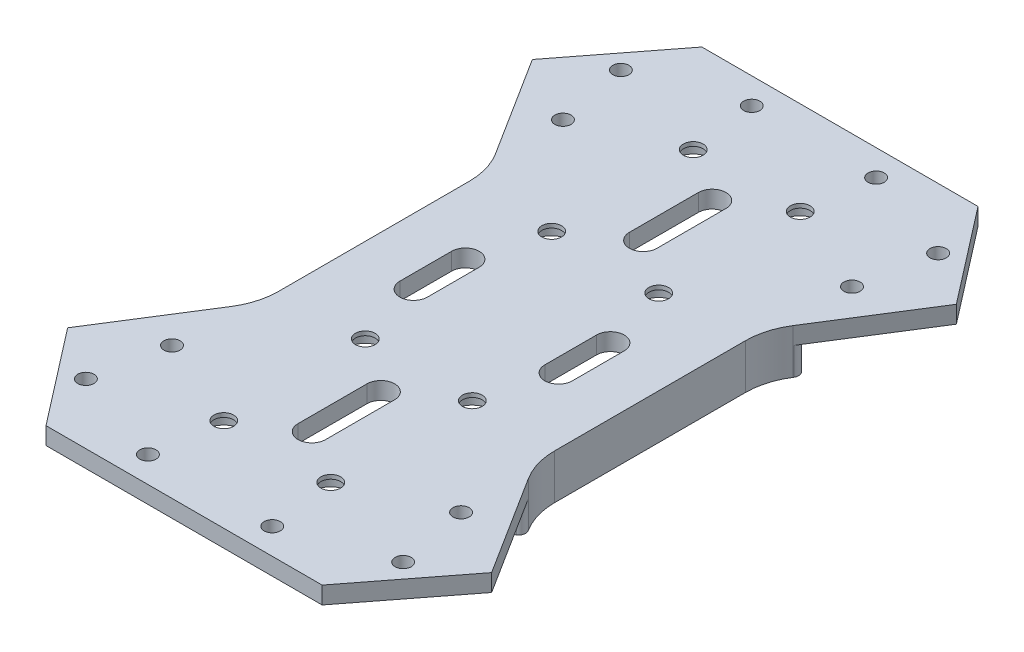
SolidWorks part; units mm, degrees
ref_plane "Plan de face" through (0, 0, 0) normal (0, 0, 1) x (1, 0, 0)
ref_plane "Plan de dessus" through (0, 0, 0) normal (0, 1, 0) x (1, 0, 0)
ref_plane "Plan de droite" through (0, 0, 0) normal (1, 0, 0) x (0, 0, -1)
sketch "Esquisse1" plane through (0, 0, 0) normal (0, 1, 0) x (1, 0, 0)
  line L0 (0, 95) -> (0, -95) construction
  line L1 (40, -95) -> (-40, -95)
  line L2 (-40, -95) -> (-61.4148, -67.316)
  line L3 (-61.4148, -67.316) -> (-40, -33.4103)
  line L4 (-40, -33.4103) -> (-40, 33.4103)
  line L5 (-40, 33.4103) -> (-61.4148, 67.316)
  line L6 (-61.4148, 67.316) -> (-40, 95)
  line L7 (-40, 95) -> (40, 95)
  line L8 (-40, -95) -> (-40, 95) construction
  line L9 (-90.2912, 0) -> (0, 0) construction
  line L10 (50.7074, 81.158) -> (185.1727, 185.1727) construction
  line L11 (-50.7074, 81.158) -> (-185.1727, 185.1727) construction
  line L12 (40, -95) -> (40, 95) construction
  line L13 (61.4148, 67.316) -> (40, 95)
  line L14 (40, 33.4103) -> (61.4148, 67.316)
  line L15 (40, -33.4103) -> (40, 33.4103)
  line L16 (61.4148, -67.316) -> (40, -33.4103)
  line L17 (40, -95) -> (61.4148, -67.316)
  line L18 (50.7074, -81.158) -> (185.1727, -185.1727) construction
  line L19 (-50.7074, -81.158) -> (-185.1727, -185.1727) construction
  line L20 (-185.1727, 185.1727) -> (185.1727, 185.1727) construction
  line L21 (-185.1727, 185.1727) -> (-185.1727, -185.1727) construction
  line L22 (-50.7074, 81.158) -> (-11.4576, 50.7965) construction
  circle A0 centre (18.0097, 87.4716) radius 2.35
  circle A1 centre (45.9616, 77.4869) radius 2.35
  circle A2 centre (41.8719, 56.6236) radius 2.35
  circle A3 centre (-41.8719, 56.6236) radius 2.35
  circle A4 centre (-45.9616, 77.4869) radius 2.35
  circle A5 centre (-18.0097, 87.4716) radius 2.35
  circle A6 centre (41.8719, -56.6236) radius 2.35
  circle A7 centre (45.9616, -77.4869) radius 2.35
  circle A8 centre (18.0097, -87.4716) radius 2.35
  circle A9 centre (-18.0097, -87.4716) radius 2.35
  circle A10 centre (-45.9616, -77.4869) radius 2.35
  circle A11 centre (-41.8719, -56.6236) radius 2.35
  dimension "D10" = 4.7
  dimension "D11" = 4.7
  dimension "D12" = 4.7
  dimension "D1" = 40
  dimension "D2" = 190
  dimension "D3" = 110
  dimension "D4" = 35
  dimension "D5" = 170
  dimension "D6" = 170
  dimension "D7" = 170
  dimension "D8" = 170
  dimension "D9" = 127.724
extrude "Boss.-Extru.1" add sketch "Esquisse1" along normal blind 5
sketch3d "Esquisse3D2" plane through (0, 0, 0) normal (0, 0, 1) x (1, 0, 0)
sketch "Esquisse2" plane through (0, 0, 0) normal (0, -1, 0) x (1, 0, 0)
  line L0 (0, -95) -> (0, 69.3313) construction
  line L1 (-36.2914, -47.5) -> (35.8719, -47.5) construction
  line L2 (40, -95) -> (-40, -95) construction
  line L3 (-47.7044, 0) -> (47.4513, 0) construction
  circle A0 centre (-15.5, -68) radius 5.5
  circle A1 centre (15.5, -68) radius 5.5
  circle A2 centre (15.5, -27) radius 5.5
  circle A3 centre (-15.5, -27) radius 5.5
  circle A4 centre (15.5, 68) radius 5.5
  circle A5 centre (-15.5, 68) radius 5.5
  circle A6 centre (15.5, 27) radius 5.5
  circle A7 centre (-15.5, 27) radius 5.5
  dimension "D1" = 11
  dimension "D2" = 15.5
  dimension "D3" = 20.5
extrude "Enlèv. mat.-Extru.1" cut sketch "Esquisse2" against normal blind 3.8
sketch "Esquisse3" plane through (0, 0, 0) normal (0, -1, 0) x (1, 0, 0)
  line L0 (-48.0842, 0) -> (48.5909, 0) construction
  circle A0 centre (-15.5, -27) radius 2.85
  circle A1 centre (15.5, -27) radius 2.85
  circle A2 centre (-15.5, -68) radius 2.85
  circle A3 centre (15.5, -68) radius 2.85
  circle A4 centre (15.5, 68) radius 2.85
  circle A5 centre (-15.5, 68) radius 2.85
  circle A6 centre (15.5, 27) radius 2.85
  circle A7 centre (-15.5, 27) radius 2.85
  dimension "D1" = 5.7
  dimension "D2" = 5.7
  dimension "D3" = 5.7
  dimension "D4" = 5.7
extrude "Enlèv. mat.-Extru.2" cut sketch "Esquisse3" against normal blind 5
sketch "Esquisse5" plane through (0, 0, 0) normal (0, -1, 0) x (1, 0, 0)
  line L0 (0, -105.2031) -> (0, 102.0565) construction
  line L1 (0, 58) -> (0, 38) construction
  line L2 (4, 58) -> (4, 38)
  line L3 (-4, 58) -> (-4, 38)
  line L4 (-46.5705, 0) -> (46.5705, 0) construction
  line L5 (-21, -7.5) -> (-21, 7.5) construction
  line L6 (-25, -7.5) -> (-25, 7.5)
  line L7 (-17, -7.5) -> (-17, 7.5)
  line L8 (21, -7.5) -> (21, 7.5) construction
  line L9 (25, -7.5) -> (25, 7.5)
  line L10 (17, -7.5) -> (17, 7.5)
  line L11 (-35.7675, 10) -> (32.6735, 10) construction
  line L15 (0, -58) -> (0, -38) construction
  line L16 (4, -58) -> (4, -38)
  line L17 (-4, -58) -> (-4, -38)
  arc A0 (4, 58) -> (-4, 58) centre (0, 58) ccw
  arc A1 (-4, 38) -> (4, 38) centre (0, 38) ccw
  arc A2 (-25, -7.5) -> (-17, -7.5) centre (-21, -7.5) ccw
  arc A3 (-17, 7.5) -> (-25, 7.5) centre (-21, 7.5) ccw
  arc A4 (25, -7.5) -> (17, -7.5) centre (21, -7.5) cw
  arc A5 (17, 7.5) -> (25, 7.5) centre (21, 7.5) cw
  arc A8 (4, -58) -> (-4, -58) centre (0, -58) cw
  arc A9 (-4, -38) -> (4, -38) centre (0, -38) cw
  point P5 (0, 48)
  point P15 (-21, 0)
  point P23 (21, 0)
  point P37 (0, -48)
  dimension "D1" = 8
  dimension "D2" = 20
  dimension "D3" = 48
  dimension "D6" = 8
  dimension "D8" = 10
  dimension "D4" = 21
  dimension "D5" = 15
extrude "Enlèv. mat.-Extru.3" cut sketch "Esquisse5" against normal blind 5
sketch "Esquisse6" plane through (0, 0, 0) normal (0, -1, 0) x (1, 0, 0)
  line L0 (40, -33.4103) -> (40, 33.4103)
  line L1 (40, 33.4103) -> (44.272, 40.1741)
  line L2 (44.272, 40.1741) -> (40.8901, 42.3102)
  line L3 (40.8901, 42.3102) -> (36, 34.5677)
  line L4 (36, 34.5677) -> (36, -34.5677)
  line L5 (40, -33.4103) -> (44.272, -40.1741)
  line L6 (44.272, -40.1741) -> (40.8901, -42.3102)
  line L7 (40.8901, -42.3102) -> (36, -34.5677)
  line L8 (40, 33.4103) -> (40, -33.4103) construction
  line L9 (61.4148, 67.316) -> (40, 33.4103) construction
  line L10 (40, -33.4103) -> (61.4148, -67.316) construction
  line L11 (0, -75.9337) -> (0, 75.2034) construction
  line L12 (-40.8901, -42.3102) -> (-36, -34.5677)
  line L13 (-44.272, -40.1741) -> (-40.8901, -42.3102)
  line L14 (-40, -33.4103) -> (-44.272, -40.1741)
  line L15 (-36, 34.5677) -> (-36, -34.5677)
  line L16 (-40.8901, 42.3102) -> (-36, 34.5677)
  line L17 (-44.272, 40.1741) -> (-40.8901, 42.3102)
  line L18 (-40, 33.4103) -> (-44.272, 40.1741)
  line L19 (-40, -33.4103) -> (-40, 33.4103)
  dimension "D1" = 4
  dimension "D2" = 4
  dimension "D3" = 4
  dimension "D4" = 8
  dimension "D5" = 8
extrude "Boss.-Extru.2" add sketch "Esquisse6" along normal blind 8
fillet "Congé2" radius 2 8 edges at (-40.8901, -4, 42.3102) (-44.272, -4, 40.1741) (-44.272, -4, -40.1741) (-40.8901, -4, -42.3102) (40.8901, -4, -42.3102) (44.272, -4, -40.1741) (40.8901, -4, 42.3102) (44.272, -4, 40.1741)
fillet "Congé3" radius 20 8 edges at (40, -1.5, -33.4103) (40, -1.5, 33.4103) (-40, -1.5, -33.4103) (-40, -1.5, 33.4103) (36, -4, -34.5677) (36, -4, 34.5677) (-36, -4, -34.5677) (-36, -4, 34.5677)
